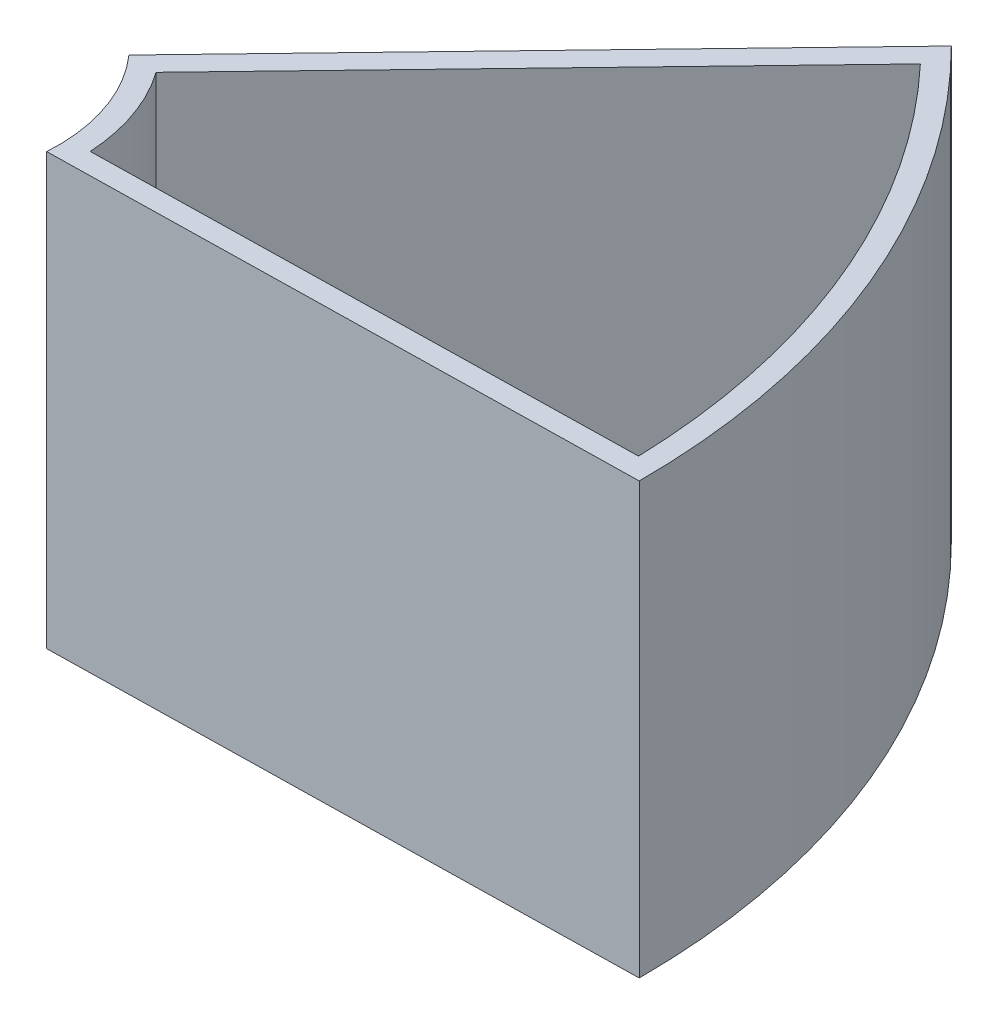
SolidWorks part; units mm, degrees
ref_plane "Front Plane" through (0, 0, 0) normal (0, 0, 1) x (1, 0, 0)
ref_plane "Top Plane" through (0, 0, 0) normal (0, 1, 0) x (1, 0, 0)
ref_plane "Right Plane" through (0, 0, 0) normal (1, 0, 0) x (0, 0, -1)
sketch "Sketch3" plane through (0, 0, 0) normal (0, 1, 0) x (1, 0, 0)
  line L0 (123.7437, 123.7437) -> (30.0457, 26.4056)
  line L1 (175, 0) -> (39.9171, -2.5739)
  line L2 (36.6721, 26.0798) -> (123.7587, 116.5495)
  line L3 (169.9292, 4.9043) -> (44.9292, 2.5225)
  arc A0 (175, 0) -> (123.7437, 123.7437) centre (0, 0) ccw
  arc A1 (39.9171, -2.5739) -> (30.0457, 26.4056) centre (0, 0) ccw
  arc A2 (36.6721, 26.0798) -> (44.9292, 2.5225) centre (0, 0) cw
  arc A3 (123.7587, 116.5495) -> (169.9292, 4.9043) centre (0, 0) cw
  dimension "D7" = 170
  dimension "D9" = 5
  dimension "D8" = 125
  dimension "D1" = 175
  dimension "D2" = 45
  dimension "D3" = 5
  dimension "D4" = 40
  dimension "D5" = 45
  dimension "D10" = 5
  dimension "D12" = 5
  dimension "D13" = 5
extrude "Boss-Extrude1" add sketch "Sketch3" along normal blind 100
sketch "Sketch5" plane through (0, 0, 0) normal (0, 1, 0) x (1, 0, 0)
  line L0 (123.7437, 123.7437) -> (30.0457, 26.4056)
  line L2 (39.9171, -2.5739) -> (175, 0)
  arc A0 (30.0457, 26.4056) -> (39.9171, -2.5739) centre (0, 0) cw
  arc A1 (175, 0) -> (123.7437, 123.7437) centre (0, 0) ccw
extrude "Boss-Extrude3" add sketch "Sketch5" along normal blind 15 contours L2 A1 L0 A0 | L0 A0 L2 A1 region at (109.8737, 0, -44.4383)
